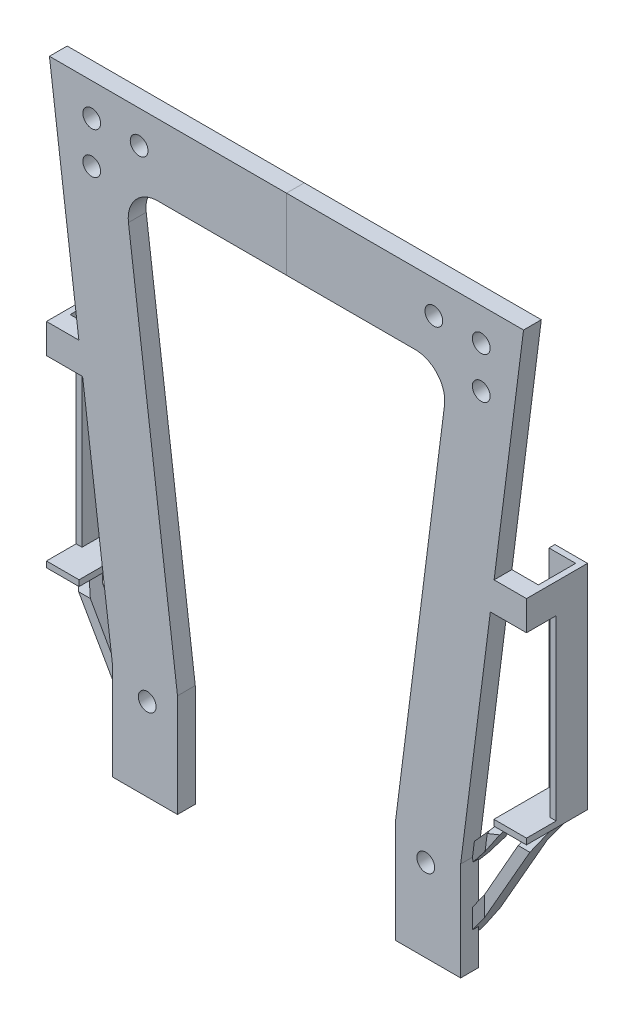
SolidWorks part; units mm, degrees
ref_plane "Plano frontal" through (0, 0, 0) normal (0, 0, 1) x (1, 0, 0)
ref_plane "Plano superior" through (0, 0, 0) normal (0, 1, 0) x (1, 0, 0)
ref_plane "Plano direito" through (0, 0, 0) normal (1, 0, 0) x (0, 0, -1)
ref_plane "Plano1" through (0, 0, -2.5) normal (0, 0, -1) x (-1, 0, 0)
sketch "Esboço8" plane through (0, 0, 0) normal (0, 0, 1) x (1, 0, 0)
  line L0 (29.3895, 0) -> (29.3895, 16.6513)
  line L1 (29.3895, 16.6513) -> (40, 100)
  line L2 (40, 100) -> (-40, 100)
  line L3 (-40, 100) -> (-29.3895, 16.6513)
  line L4 (-29.3895, 16.6513) -> (-29.3895, 0)
  line L5 (-29.3895, 0) -> (-18.3895, 0)
  line L6 (-18.3895, 0) -> (-18.3895, 17.3487)
  line L7 (-18.3895, 17.3487) -> (-27.3836, 88)
  line L8 (-27.3836, 88) -> (27.3836, 88)
  line L9 (27.3836, 88) -> (18.3895, 17.3487)
  line L10 (18.3895, 17.3487) -> (18.3895, 0)
  line L11 (18.3895, 0) -> (29.3895, 0)
  line L12 (-28.956, 13.2454) -> (-18.044, 14.6346) construction
  line L13 (28.956, 13.2454) -> (18.044, 14.6346) construction
  line L14 (23.5, 13.94) -> (-23.5, 13.94) construction
  line L15 (55, 0) -> (-55, 0) construction
  line L16 (29.3895, 16.6513) -> (18.3895, 17.3487) construction
  line L17 (0, 100) -> (0, 88)
  line L18 (-29.3895, 16.6513) -> (-18.3895, 17.3487) construction
  line L19 (23.5, 12.44) -> (23.5, 0) construction
  line L20 (23.8895, 17) -> (23.8895, 0) construction
  line L21 (-23.8895, 17) -> (-23.8895, 0) construction
  line L22 (32.8643, 93) -> (32.8643, 89) construction
  line L23 (31.3643, 94.5) -> (26.3643, 94.5) construction
  line L24 (24.8643, 96) -> (24.8643, 100) construction
  line L25 (34.3523, 87.3106) -> (38.3203, 86.8054) construction
  circle A0 centre (23.5, 13.94) radius 1.5
  circle A1 centre (-23.5, 13.94) radius 1.5
  circle A2 centre (32.8643, 94.5) radius 1.5
  circle A3 centre (24.8643, 94.5) radius 1.5
  circle A4 centre (32.8643, 87.5) radius 1.5
  point P18 (-23.5, 13.94)
  point P21 (23.5, 13.94)
  point P22 (0, 13.94)
  point P26 (0, 100)
  dimension "D9" = 3
  dimension "D14" = 3
  dimension "D1" = 11
  dimension "D2" = 11
  dimension "D3" = 11
  dimension "D4" = 11
  dimension "D5" = 100
  dimension "D6" = 12
  dimension "D7" = 80
  dimension "D8" = 13.94
  dimension "D10" = 47
  dimension "D11" = 12.44
  dimension "D12" = 17
  dimension "D13" = 17
  dimension "D15" = 5
  dimension "D16" = 4
  dimension "D17" = 4
  dimension "D18" = 4
ref_plane "Plano4" through (0, 25, 0) normal (0, 1, 0) x (1, 0, 0)
extrude "Ressalto-extrusão3" add sketch "Esboço8" along normal blind 3 separate body contours L2 L17 L8 L9 L10 L11 L0 L1 A0 region at (24.8897, 60.0952, 0)
sketch "Esboço7" plane through (0, 25, 0) normal (0, -1, 0) x (-1, 0, 0)
  line L0 (-18.3895, -3) -> (-29.3895, -3) construction
  line L5 (-35, 2) -> (-40.5, 2)
  line L6 (-35, 2) -> (-35, 7.3)
  line L7 (-35, 7.3) -> (-40.5, 7.3)
  line L8 (-40.5, 2) -> (-40.5, 7.3)
  line L9 (0, 55) -> (0, -55) construction
  dimension "D1" = 5
  dimension "D2" = 40.5
  dimension "D3" = 5.5
  dimension "D4" = 5.3
extrude "Ressalto-extrusão2" add sketch "Esboço7" against normal blind 36 separate body contours L8 L7 L6 L5
shell "Casca1" thickness 1 removed face at (37.75, 43, -2) removed face at (35, 43, -4.65) removed face at (37.75, 61, -4.65)
sketch "Esboço10" plane through (0, 0, 3) normal (0, 0, 1) x (1, 0, 0)
  line L0 (28.0015, 3.6108) -> (40.5, 25.4632)
  line L6 (34.5416, 25.0604) -> (34.5416, 23.5217) construction
  line L7 (34.5416, 23.5217) -> (28.7895, 15)
  line L8 (28.7895, 15) -> (28.7895, 18)
  line L9 (28.7895, 18) -> (34.5416, 25.0604)
  line L10 (28.0015, 3.6108) -> (28.0015, 6.9108)
  line L11 (28.0015, 6.9108) -> (38.5, 25.4632)
  line L12 (38.5, 25.4632) -> (40.5, 25.4632)
  line L13 (34.5416, 23.5217) -> (35.9643, 25.6295)
  line L14 (34.5416, 25.0604) -> (35.9643, 25.6295)
  line L16 (40.5, 61) -> (40.5, 25) construction
  line L17 (18.3895, 0) -> (29.3895, 0) construction
  line L18 (29.3895, 0) -> (29.3895, 16.6513) construction
  dimension "D2" = 3
  dimension "D4" = 2
  dimension "D5" = 3.3
  dimension "D6" = 111.801
  dimension "D7" = 15
  dimension "D8" = 0.6
extrude "Ressalto-extrusão4" add sketch "Esboço10" against normal blind 2.5 from offset 3 contours L11 L12 L0 L10 offset against normal yes
extrude "Ressalto-extrusão5" add sketch "Esboço10<3>" against normal blind 2.5 from offset 3 contours L7 L8 L9 L14 L13 offset against normal yes
sketch "Esboço10<3>" plane through (0, 0, 3) normal (0, 0, 1) x (1, 0, 0) same geometry as "Esboço10"
chamfer "Chanfro1" distance 1 angle 45 2 edges at (29.5468, 17.887, 0) (29.3895, 7.7007, 0)
chamfer "Chanfro2" distance 1.5 angle 60 2 edges at (28.0015, 5.2608, -2.5) (28.7895, 16.5, -2.5) first distance on face at (28.0015, 5.2608, -1.25) first distance on face at (28.7895, 16.5, -1.25)
chamfer "Chanfro3" distance 3 angle 30 1 edges at (39.2365, 25, -2.5) first distance on face at (34.918, 17.4138, -2.5)
chamfer "Chanfro4" distance 4.25 angle 25 1 edges at (39.5, 25.4632, 0) first distance on face at (34.9448, 17.4608, 0)
chamfer "Chanfro5" distance 0.5 angle 85 2 edges at (35.2697, 25, -2.5) (35, 25.1219, -2.5) first distance on face at (37.9025, 25, -3.6064) first distance on face at (35, 34.3109, -4.525)
chamfer "Chanfro6" distance 3 angle 30 1 edges at (35.2529, 25.3449, 0) first distance on face at (32.9793, 22.2078, 0)
chamfer "Chanfro7" distance 1 angle 30 2 edges at (28.7895, 16.5, -1) (28.0015, 5.2608, -1) first distance on face at (30.4193, 18.5516, -1.9409) first distance on face at (29.3005, 7.5442, -1.75)
sketch "Esboço11" plane through (0, 61, 0) normal (0, 1, 0) x (1, 0, 0)
  line L0 (40.5, 2) -> (40.5, -3)
  line L1 (40.5, -3) -> (31.581, -3)
  line L2 (31.581, -3) -> (31.581, 0)
  line L3 (31.581, 0) -> (39.5, 0)
  line L4 (39.5, 0) -> (39.5, 2)
  line L5 (39.5, 2) -> (40.5, 2) construction
  line L6 (39.5, 2) -> (39.5, 6.3) construction
  line L7 (40.5, 2) -> (39.5, 2)
  dimension "D1" = 3
extrude "Ressalto-extrusão6" add sketch "Esboço11" against normal blind 5
sketch "Esboço12" plane through (0, 0, -2) normal (0, 0, 1) x (1, 0, 0)
  line L0 (35, 26) -> (40.5, 26)
  line L1 (40.5, 56) -> (40.5, 25.4632) construction
  line L2 (40.5, 26) -> (40.5, 25)
  line L3 (40.5, 25) -> (35, 25)
  line L4 (35, 25) -> (35, 26)
extrude "Ressalto-extrusão7" add sketch "Esboço12" along normal up to surface (5 mm away) up to face at (26.1146, 53.6667, 3)
fillet "Filete1" radius 5 1 edges at (27.3836, 88, 1.5)
mirror "Espelhar2" about plane through (0, 0, 0) normal (1, 0, 0) of bodies 124 109 117
